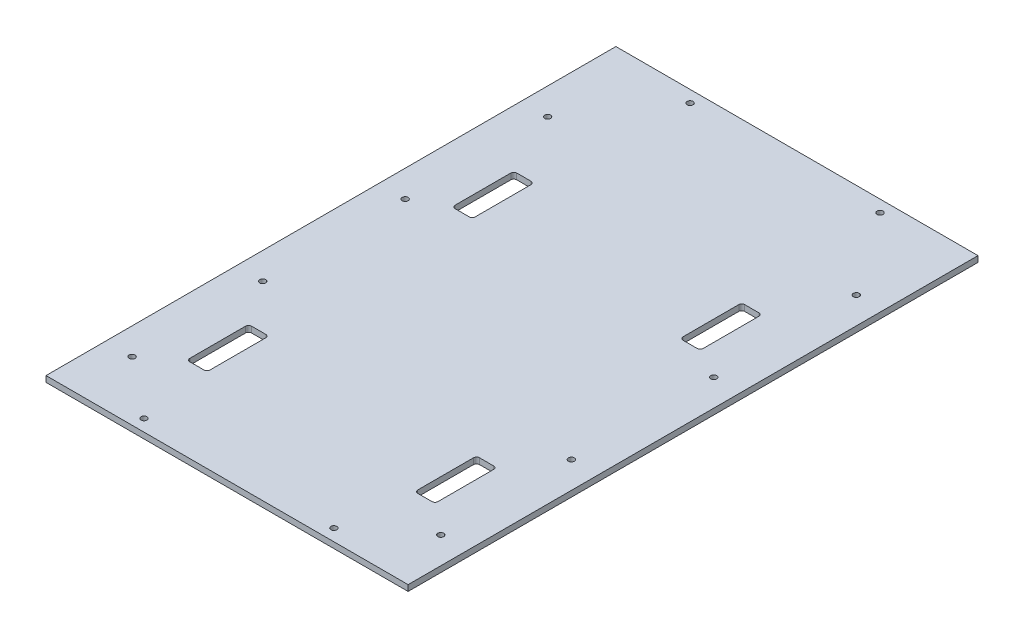
SolidWorks part; units mm, degrees
ref_plane "Front Plane" through (0, 0, 0) normal (0, 0, 1) x (1, 0, 0)
ref_plane "Top Plane" through (0, 0, 0) normal (0, 1, 0) x (1, 0, 0)
ref_plane "Right Plane" through (0, 0, 0) normal (1, 0, 0) x (0, 0, -1)
sketch "Sketch1" plane through (0, 0, 0) normal (0, 1, 0) x (1, 0, 0)
  line L1 (-193.675, -304.8) -> (193.675, -304.8)
  line L2 (-193.675, -304.8) -> (-193.675, 304.8)
  line L3 (-193.675, 304.8) -> (193.675, 304.8)
  line L4 (193.675, -304.8) -> (193.675, 304.8)
  line L5 (0, 304.8) -> (0, -304.8) construction
  line L6 (-193.675, 0) -> (193.675, 0) construction
  point P0 (0, 0)
  dimension "D1" = 387.35
  dimension "D2" = 609.6
extrude "Boss-Extrude1" add sketch "Sketch1" along normal blind 6.35
sketch "Sketch2" plane through (0, 6.35, 0) normal (0, 1, 0) x (1, 0, 0)
  line L0 (0, -1000) -> (0, 49000) construction
  line L6 (111.125, -215.138) -> (132.715, -215.138)
  line L7 (111.125, 68.58) -> (132.715, 68.58)
  line L8 (111.125, 68.58) -> (111.125, 134.62)
  line L9 (111.125, 134.62) -> (132.715, 134.62)
  line L10 (132.715, 68.58) -> (132.715, 134.62)
  line L11 (121.92, 134.62) -> (121.92, 68.58) construction
  line L12 (111.125, 101.6) -> (132.715, 101.6) construction
  line L17 (111.125, -215.138) -> (111.125, -149.098)
  line L18 (111.125, -149.098) -> (132.715, -149.098)
  line L23 (132.715, -215.138) -> (132.715, -149.098)
  line L24 (121.92, -149.098) -> (121.92, -215.138) construction
  line L25 (111.125, -182.118) -> (132.715, -182.118) construction
  line L26 (-121.92, -149.098) -> (-121.92, -215.138) construction
  line L27 (-132.715, -215.138) -> (-132.715, -149.098)
  line L28 (-111.125, -215.138) -> (-111.125, -149.098)
  line L29 (-111.125, -215.138) -> (-132.715, -215.138)
  line L30 (-111.125, -182.118) -> (-132.715, -182.118) construction
  line L31 (-111.125, -149.098) -> (-132.715, -149.098)
  line L32 (-111.125, 101.6) -> (-132.715, 101.6) construction
  line L33 (-121.92, 134.62) -> (-121.92, 68.58) construction
  line L34 (-132.715, 68.58) -> (-132.715, 134.62)
  line L35 (-111.125, 134.62) -> (-132.715, 134.62)
  line L36 (-111.125, 68.58) -> (-111.125, 134.62)
  line L37 (-111.125, 68.58) -> (-132.715, 68.58)
  line L38 (193.675, 304.8) -> (-193.675, 304.8) construction
  point P1 (121.92, -182.118)
  point P4 (121.92, 101.6)
  point P20 (-121.92, -182.118)
  point P29 (-121.92, 101.6)
  dimension "D1" = 66.04
  dimension "D2" = 21.59
  dimension "D3" = 66.04
  dimension "D4" = 283.718
  dimension "D5" = 203.2
  dimension "D6" = 121.92
extrude "Cut-Extrude1" cut sketch "Sketch2" against normal through all
fillet "Fillet1" radius 3.175 16 edges at (-132.715, 3.175, -134.62) (-111.125, 3.175, -134.62) (132.715, 3.175, 215.138) (132.715, 3.175, 149.098) (111.125, 3.175, 149.098) (111.125, 3.175, 215.138) (-111.125, 3.175, 215.138) (-132.715, 3.175, 215.138) (-111.125, 3.175, 149.098) (-132.715, 3.175, 149.098) (132.715, 3.175, -68.58) (111.125, 3.175, -68.58) (132.715, 3.175, -134.62) (111.125, 3.175, -134.62) (-111.125, 3.175, -68.58) (-132.715, 3.175, -68.58)
ref_plane "front_wheel" through (0, 0, -101.6) normal (0, 0, 1) x (1, 0, 0)
ref_plane "back_wheel" through (0, 0, 182.118) normal (0, 0, 1) x (1, 0, 0)
ref_plane "stream_midplane" through (0, 0, 0) normal (0, 0, 1) x (1, 0, 0)
sketch "Sketch3" plane through (0, 0, 0) normal (0, -1, 0) x (-1, 0, 0)
  line L0 (-193.675, 304.8) -> (193.675, 304.8) construction
  line L3 (-3.4925, 0) -> (3.4925, 0) construction
  line L4 (193.675, -304.8) -> (-193.675, -304.8) construction
  line L5 (0, 3.4925) -> (0, -3.4925) construction
  line L6 (-3.4925, 0) -> (3.4925, 0) construction
  circle A0 centre (101.6, 292.1) radius 3.175
  circle A1 centre (165.1, 203.2) radius 3.175
  circle A2 centre (165.1, -101.6) radius 3.175
  circle A3 centre (165.1, 50.8) radius 3.175
  circle A5 centre (165.1, -241.3) radius 3.175
  circle A6 centre (-165.1, -241.3) radius 3.175
  circle A7 centre (-165.1, -101.6) radius 3.175
  circle A8 centre (-165.1, 50.8) radius 3.175
  circle A9 centre (-165.1, 203.2) radius 3.175
  circle A10 centre (-101.6, 292.1) radius 3.175
  circle A11 centre (101.6, -292.1) radius 3.175
  circle A12 centre (-101.6, -292.1) radius 3.175
  point P19 (168.275, -101.6)
  point P20 (168.275, -241.3)
  point P39 (0, 0)
  point P40 (0, 0)
  dimension "D1" = 6.35
  dimension "D2" = 6.35
  dimension "D6" = 6.35
  dimension "D10" = 6.35
  dimension "D3" = 12.7
  dimension "D4" = 165.1
  dimension "D5" = 101.6
  dimension "D7" = 101.6
  dimension "D9" = 101.6
  dimension "D8" = 50.8
  dimension "D11" = 63.5
  dimension "D12" = 165.1
extrude "Cut-Extrude2" cut sketch "Sketch3" against normal through all
